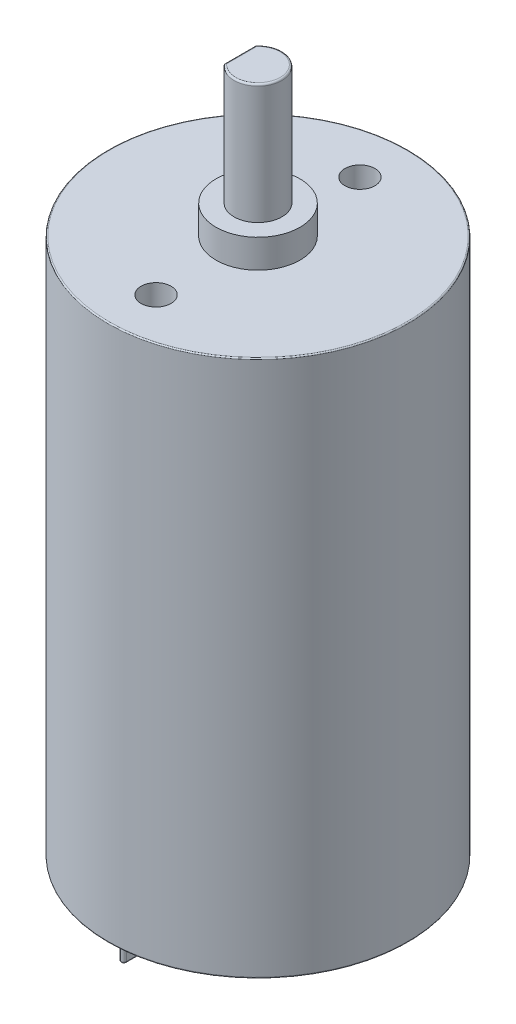
SolidWorks part; units mm, degrees
note: The reader was unsure of these and kept them because the rebuilt part matched: shared geometry of "Esboço7<5>", "Esboço11<2>", "Esboço11<4>".
ref_plane "Plano frontal" through (0, 0, 0) normal (0, 0, 1) x (1, 0, 0)
ref_plane "Plano superior" through (0, 0, 0) normal (0, 1, 0) x (1, 0, 0)
ref_plane "Plano direito" through (0, 0, 0) normal (1, 0, 0) x (0, 0, -1)
sketch "Esboço2" plane through (0, 0, 0) normal (0, 1, 0) x (1, 0, 0)
  line L0 (0, 8.5) -> (0, -8.5) construction
  circle A0 centre (0, 0) radius 12.5
  circle A1 centre (0, 0) radius 3.5
  circle A2 centre (0, 0) radius 2
  point P8 (0, 0)
  dimension "D1" = 25
  dimension "D2" = 7
  dimension "D3" = 4
  dimension "D4" = 17
extrude "Ressalto-extrusão2" add sketch "Esboço2" along normal blind 44.8 contours A0
sketch "Esboço7" plane through (0, 0, 0) normal (0, -1, 0) x (1, 0, 0)
  line L0 (1.5, -8.3101) -> (1.5, -9.6899) construction
  line L1 (-1.5005, 9) -> (1.5005, 9) construction
  line L2 (-1.5005, 10.5) -> (1.5005, 10.5)
  line L3 (-1.5005, 7.5) -> (1.5005, 7.5)
  line L4 (-1.5, -9) -> (1.5, -9) construction
  line L5 (-1.5, -7.5) -> (1.5, -7.5)
  line L6 (-1.5, -10.5) -> (1.5, -10.5)
  line L12 (-1.5005, 9.6899) -> (-1.5005, 8.3101) construction
  line L13 (-1.2833, 9.6899) -> (-1.2833, 8.3101)
  line L14 (-1.7176, 9.6899) -> (-1.7176, 8.3101)
  line L18 (1.7171, -8.3101) -> (1.7171, -9.6899)
  line L19 (1.2829, -8.3101) -> (1.2829, -9.6899)
  arc A0 (-1.5005, 10.5) -> (-1.5005, 7.5) centre (-1.5005, 9) ccw
  arc A1 (1.5005, 7.5) -> (1.5005, 10.5) centre (1.5005, 9) ccw
  arc A2 (-1.5, -7.5) -> (-1.5, -10.5) centre (-1.5, -9) ccw
  arc A3 (1.5, -10.5) -> (1.5, -7.5) centre (1.5, -9) ccw
  arc A4 (-1.2833, 9.6899) -> (-1.7176, 9.6899) centre (-1.5005, 9.6899) ccw
  arc A5 (-1.7176, 8.3101) -> (-1.2833, 8.3101) centre (-1.5005, 8.3101) ccw
  arc A8 (1.7171, -8.3101) -> (1.2829, -8.3101) centre (1.5, -8.3101) ccw
  arc A9 (1.2829, -9.6899) -> (1.7171, -9.6899) centre (1.5, -9.6899) ccw
  circle A11 centre (0, 0) radius 3
  point P4 (0, 9)
  point P6 (0, 0)
  point P14 (0, -9)
  point P19 (-1.5005, 9)
  point P21 (-1.5005, 9)
  point P29 (1.5, -9)
  dimension "D1" = 6
  dimension "D2" = 3
  dimension "D3" = 3
extrude "Ressalto-extrusão7" add sketch "Esboço7" along normal blind 3.5 contours L18 A9 L19 A8 | L14 A5 L13 A4
fillet "Filete9" radius 0.1 10 edges at (1.5, -3.5, -8.093) (1.7171, -3.5, -9) (1.5, -3.5, -9.907) (-1.2833, -3.5, 9) (-1.5005, -3.5, 8.093) (0, 0, 12.5) (0, 44.8, 12.5) (1.2829, -3.5, -9) (-1.7176, -3.5, 9) (-1.5005, -3.5, 9.907)
extrude "Ressalto-extrusão8" add sketch "Esboço7<5>" along normal blind 2.6 contours A11
sketch "Esboço7<5>" plane through (0, 0, 0) normal (0, -1, 0) x (1, 0, 0) same geometry as "Esboço7"
fillet "Filete10" radius 1 1 edges at (0, -2.6, -3)
sketch "Esboço11" plane through (0, 44.8, 0) normal (0, 1, 0) x (1, 0, 0)
  circle A0 centre (0, 0) radius 3.5
  circle A1 centre (0, 0) radius 2
  point P2 (0, 8.5)
  point P7 (0, 0)
  point P15 (0, 8.5)
  point P18 (0, -8.5)
  dimension "D2" = 4
  dimension "D3" = 7
hole_wizard "Furo roscado de M31" positions "Esboço11" profile "Esboço12" tap size "M3" standard "ISO"
sketch "Esboço12" plane through (0, 44.8, 8.5) normal (1, 0, 0) x (0, 0, 1)
  line L0 (0, 0) -> (0, 4.2511)
  line L1 (0, 4.2511) -> (1.25, 3.5)
  line L2 (1.25, 3.5) -> (1.25, 0)
  line L5 (1.25, 0) -> (0, 0)
  line L10 (0, 4.2511) -> (-1.25, 3.5) construction
  line L11 (0, -6.35) -> (0, 107.95) construction
  dimension "Tap Drill Dia." = 2.5
  dimension "Tap Drill Depth" = 3.5
  dimension "Drill Angle" = 118
cosmetic thread "Rosca de furo4" parameters "D1"=3, "D2"=3
cosmetic thread "Rosca de furo6" parameters "D1"=3, "D2"=3
extrude "Ressalto-extrusão9" add sketch "Esboço11<2>" along normal blind 2.38
sketch "Esboço11<2>" plane through (0, 44.8, 0) normal (0, 1, 0) x (1, 0, 0) same geometry as "Esboço11"
extrude "Ressalto-extrusão10" add sketch "Esboço11<4>" along normal blind 12.38 contours A1
sketch "Esboço11<4>" plane through (0, 44.8, 0) normal (0, 1, 0) x (1, 0, 0) same geometry as "Esboço11"
sketch "Esboço13" plane through (0, 57.18, 0) normal (0, 1, 0) x (1, 0, 0)
  line L1 (-1.5105, 1.3109) -> (-1.5105, -1.3109)
  circle A0 centre (0, 0) radius 2 construction
  arc A1 (-1.5105, 1.3109) -> (-1.5105, -1.3109) centre (0, 0) ccw
  point P8 (-1.5105, 0)
extrude "Corte-extrusão1" cut sketch "Esboço13" against normal blind 8 contours A1 L1
fillet "Filete11" radius 0.15 2 edges at (-1.5105, 57.18, 0) (2, 57.18, 0)
